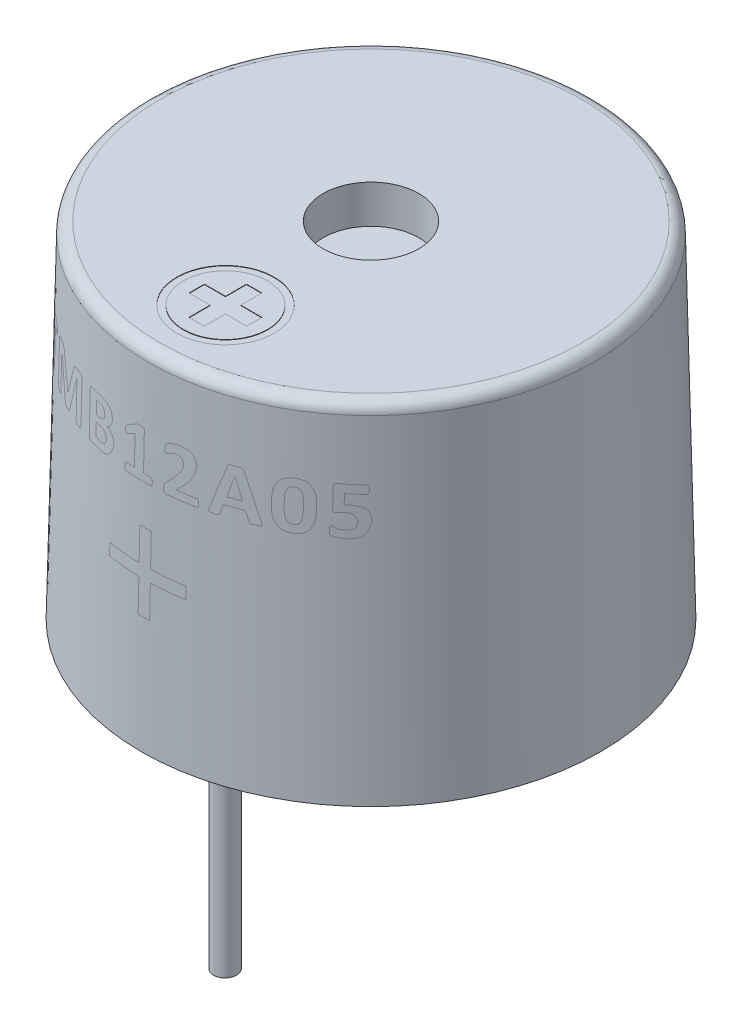
SolidWorks part; units mm, degrees
material "ABS"
ref_plane "Front Plane" through (0, 0, 0) normal (0, 0, 1) x (1, 0, 0)
ref_plane "Top Plane" through (0, 0, 0) normal (0, 1, 0) x (1, 0, 0)
ref_plane "Right Plane" through (0, 0, 0) normal (1, 0, 0) x (0, 0, -1)
sketch "Sketch1" plane through (0, 0, 0) normal (0, 0, 1) x (1, 0, 0)
  line L0 (0, 0) -> (0, 9)
  line L1 (0, 0) -> (6, 0)
  line L2 (6, 0) -> (5.8, 9)
  line L3 (5.8, 9) -> (0, 9)
  dimension "D1" = 6
  dimension "D2" = 9
  dimension "D3" = 5.8
revolve "Revolve1" add sketch "Sketch1" angle 360 about L0
sketch "Sketch2" plane through (0, 0, 0) normal (0, -1, 0) x (1, 0, 0)
  line L0 (0, 0) -> (0, 5.4) construction
  line L1 (0, 5.4) -> (0, 6) construction
  circle A0 centre (0, 0) radius 5.4
  circle A1 centre (0, 0) radius 6 construction
  dimension "D1" = 0.6
extrude "Cut-Extrude1" cut sketch "Sketch2" against normal blind 0.5
fillet "Fillet1" radius 1 1 edges at (0, 0.5, -5.4)
fillet "Fillet2" radius 0.3 1 edges at (0, 9, -5.8)
sketch "Sketch4" plane through (0, 0.5, 0) normal (0, -1, 0) x (1, 0, 0)
  line L0 (0, 3.81) -> (0, -3.81) construction
  circle A0 centre (0, -3.81) radius 0.3
  circle A1 centre (0, 3.81) radius 0.3
  dimension "D2" = 0.6
  dimension "D1" = 7.62
extrude "Boss-Extrude2" add sketch "Sketch4" along normal blind 5
sketch "Sketch5" plane through (0, 9, 0) normal (0, 1, 0) x (1, 0, 0)
  line L0 (0, 0) -> (0, -3.8) construction
  circle A0 centre (0, -3.8) radius 1.27
  circle A1 centre (0, -3.8) radius 1.1
  dimension "D1" = 2.54
  dimension "D2" = 2.2
  dimension "D3" = 3.8
extrude "Cut-Extrude2" cut sketch "Sketch5" against normal blind 0.01
sketch "Sketch6" plane through (0, 9, 0) normal (0, 1, 0) x (1, 0, 0)
  line L0 (-1.1, -3.8) -> (-0.75, -3.8) construction
  line L1 (1.1, -3.8) -> (0.75, -3.8) construction
  line L2 (0.75, -3.8) -> (0, -3.8) construction
  line L3 (0, -3.8) -> (-0.75, -3.8) construction
  line L4 (0, -3.8) -> (0, -3.05) construction
  line L5 (0, -3.05) -> (0, -2.7) construction
  line L6 (0, -3.8) -> (0, -4.55) construction
  line L7 (0, -4.55) -> (0, -4.9) construction
  line L8 (-0.2, -3.05) -> (0.2, -3.05)
  line L9 (-0.2, -4.55) -> (0.2, -4.55)
  line L10 (0.75, -3.6) -> (0.75, -4)
  line L11 (-0.75, -3.6) -> (-0.75, -4)
  line L12 (-0.75, -3.6) -> (-0.2, -3.6)
  line L13 (-0.2, -3.6) -> (-0.2, -3.05)
  line L14 (0.2, -3.05) -> (0.2, -3.6)
  line L15 (0.2, -3.6) -> (0.75, -3.6)
  line L16 (0.75, -4) -> (0.2, -4)
  line L17 (0.2, -4) -> (0.2, -4.55)
  line L18 (-0.75, -4) -> (-0.2, -4)
  line L19 (-0.2, -4) -> (-0.2, -4.55)
  line L20 (-0.2, -4) -> (-0.2, -3.6) construction
  line L21 (-0.2, -3.6) -> (0.2, -3.6) construction
  line L22 (0.2, -3.6) -> (0.2, -4) construction
  line L23 (0.2, -4) -> (-0.2, -4) construction
  circle A0 centre (0, -3.8) radius 1.1 construction
  circle A1 centre (0, -3.8) radius 1.1 construction
  dimension "D1" = 0.4
  dimension "D2" = 1.5
extrude "Cut-Extrude3" cut sketch "Sketch6" against normal blind 0.01
sketch "Sketch7" plane through (0, 9, 0) normal (0, 1, 0) x (1, 0, 0)
  circle A0 centre (0, 0) radius 1.25
  dimension "D1" = 2.5
extrude "Cut-Extrude4" cut sketch "Sketch7" against normal blind 3
sketch "Sketch8" plane through (0, 6, 0) normal (0, 1, 0) x (1, 0, 0)
  circle A0 centre (0, 0) radius 4.5
  dimension "D1" = 9
extrude "Cut-Extrude5" cut sketch "Sketch8" along normal blind 2
ref_plane "Plane1" through (0, 0, 7) normal (0, 0, 1) x (1, 0, 0)
sketch "Sketch9" plane through (0, 0, 7) normal (0, 0, 1) x (1, 0, 0)
  line L0 (0, 0) -> (0, 3) construction
  line L1 (0, 3) -> (0, 5) construction
  line L2 (1, 4) -> (-1, 4) construction
  line L3 (-1, 4.15) -> (-1, 3.85)
  line L4 (1, 4.15) -> (1, 3.85)
  line L5 (-0.15, 5) -> (0.15, 5)
  line L6 (0.15, 3) -> (-0.15, 3)
  line L7 (0.15, 5) -> (0.15, 4.15)
  line L8 (0.15, 4.15) -> (1, 4.15)
  line L9 (-0.15, 5) -> (-0.15, 4.15)
  line L10 (-0.15, 4.15) -> (-1, 4.15)
  line L11 (-1, 3.85) -> (-0.15, 3.85)
  line L12 (-0.15, 3.85) -> (-0.15, 3)
  line L13 (1, 3.85) -> (0.15, 3.85)
  line L14 (0.15, 3.85) -> (0.15, 3)
  line L15 (-0.15, 4.15) -> (0.15, 4.15) construction
  line L16 (0.15, 4.15) -> (0.15, 3.85) construction
  line L17 (0.15, 3.85) -> (-0.15, 3.85) construction
  line L18 (-0.15, 3.85) -> (-0.15, 4.15) construction
  line L19 (0, 5) -> (0, 6) construction
  line L20 (-5, 6) -> (5, 6) construction
  text T0 "TMB12A05" font "Calibri" height 1.2
  point P6 (0, 4)
  dimension "D1" = 0.3
  dimension "D2" = 2
  dimension "D3" = 2
  dimension "D4" = 4
  dimension "D5" = 1
  dimension "D6" = 10
wrap "Wrap1" sketch "Sketch9" wrap type scribe source sketch "Sketch9"
sketch "Sketch10" plane through (0, -4.5, 0) normal (0, -1, 0) x (1, 0, 0)
  circle A1 centre (0, 3.81) radius 0.3
  circle A2 centre (0, 3.81) radius 0.3
  dimension "D1" = 0
extrude "Boss-Extrude3" add sketch "Sketch10" along normal blind 1.5
